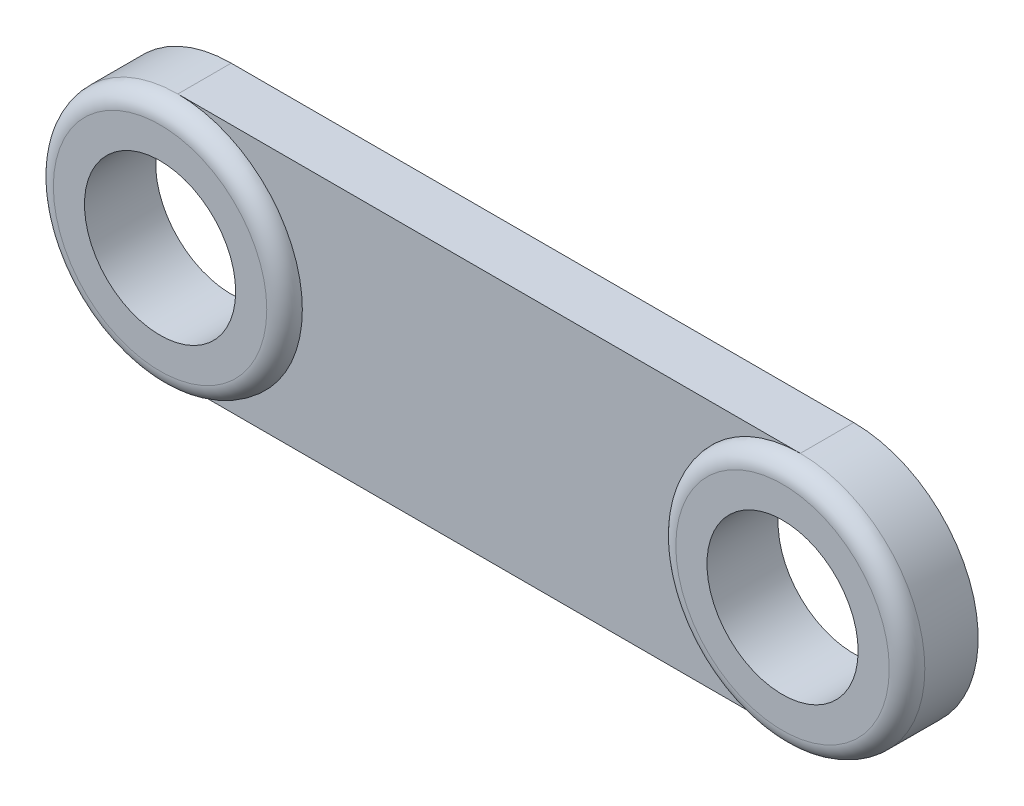
SolidWorks part; units mm, degrees
material "ABS"
ref_plane "Front Plane" through (0, 0, 0) normal (0, 0, 1) x (1, 0, 0)
ref_plane "Top Plane" through (0, 0, 0) normal (0, 1, 0) x (1, 0, 0)
ref_plane "Right Plane" through (0, 0, 0) normal (1, 0, 0) x (0, 0, -1)
sketch "Sketch1" plane through (0, 0, 0) normal (0, 0, 1) x (1, 0, 0)
  line L0 (0, 26) -> (0, 33.5) construction
  line L1 (9, -33.5) -> (-26, -33.5)
  line L3 (10, 33.5) -> (-10, 33.5)
  line L4 (-15, -14.5) -> (-15, 28.5)
  line L5 (14.0406, -31.3572) -> (-15, 33.5) construction
  line L6 (15, 33.5) -> (-15, -33.5) construction
  line L7 (-10, 28.5) -> (10, 28.5)
  line L8 (-10, 28.5) -> (-10, 23.5)
  line L9 (-10, 23.5) -> (10, 23.5)
  line L10 (10, 28.5) -> (10, 23.5)
  line L11 (-10, 28.5) -> (10, 23.5) construction
  line L12 (-10, 23.5) -> (10, 28.5) construction
  line L13 (9, -26.5) -> (-26, -26.5) construction
  line L14 (-26, -19.5) -> (-20, -19.5)
  line L15 (15, -22.8944) -> (15, 28.5)
  line L16 (-15, -19.5) -> (-15, -33.5) construction
  line L17 (15, -22.8944) -> (15, -33.5) construction
  line L18 (14.0406, -31.3572) -> (15, -33.5) construction
  circle A0 centre (9, -26.5) radius 4.25
  circle A1 centre (-26, -26.5) radius 4.25
  arc A2 (-26, -19.5) -> (-26, -33.5) centre (-26, -26.5) ccw
  arc A3 (9, -33.5) -> (15, -22.8944) centre (9, -26.5) ccw
  arc A4 (-20, -19.5) -> (-15, -14.5) centre (-20, -14.5) ccw
  arc A5 (15, 28.5) -> (10, 33.5) centre (10, 28.5) ccw
  arc A6 (-10, 33.5) -> (-15, 28.5) centre (-10, 28.5) ccw
  point P0 (0, 0)
  point P5 (0, 26)
  dimension "D6" = 8.5
  dimension "D7" = 35
  dimension "D8" = 7
  dimension "D9" = 6
  dimension "D10" = 8.5
  dimension "D11" = 14
  dimension "D12" = 5
  dimension "D1" = 30
  dimension "D2" = 33.5
  dimension "D3" = 20
  dimension "D4" = 5
  dimension "D5" = 5
extrude "Boss-Extrude1" add sketch "Sketch1" along normal blind 3
sketch "Sketch2" plane through (0, 0, 3) normal (0, 0, 1) x (1, 0, 0)
  circle A0 centre (-26, -26.5) radius 7
  circle A1 centre (9, -26.5) radius 7
  circle A2 centre (-26, -26.5) radius 4.25
  circle A3 centre (9, -26.5) radius 4.25
  circle A4 centre (-26, -26.5) radius 4.25 construction
  circle A5 centre (9, -26.5) radius 4.25 construction
  arc A6 (-26, -19.5) -> (-26, -33.5) centre (-26, -26.5) ccw construction
  arc A7 (9, -33.5) -> (15, -22.8944) centre (9, -26.5) ccw construction
extrude "Boss-Extrude2" add sketch "Sketch2" along normal blind 1
fillet "Fillet1" radius 1 2 edges at (16, -26.5, 4) (-19, -26.5, 4)
sketch "Sketch3" plane through (0, 0, 3) normal (0, 0, 1) x (1, 0, 0)
  line L0 (10, 33.5) -> (-10, 33.5) construction
  line L1 (-20, -19.5) -> (9, -19.5)
  line L2 (-20, -19.5) -> (-20, 33.5)
  line L3 (-20, 33.5) -> (15, 33.5)
  line L4 (15, -22.8944) -> (15, 33.5)
  line L5 (15, -22.8944) -> (15, 28.5) construction
  arc A0 (-20, -19.5) -> (-15, -14.5) centre (-20, -14.5) ccw construction
  arc A1 (15, -22.8944) -> (9, -19.5) centre (9, -26.5) ccw
extrude "Cut-Extrude1" cut sketch "Sketch3" against normal through all
